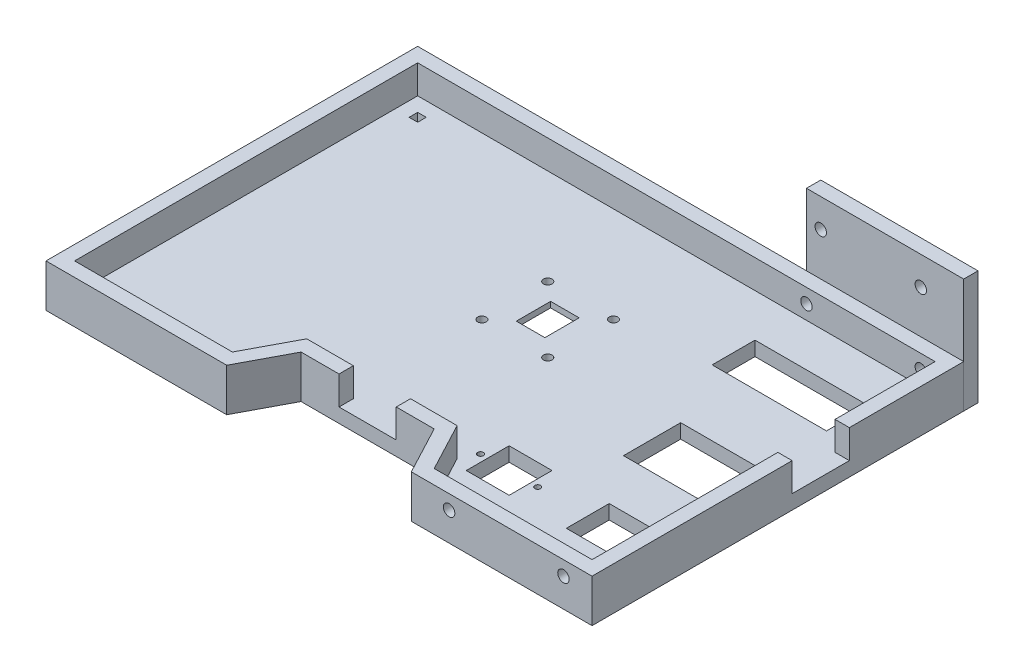
SolidWorks part; units mm, degrees
ref_plane "Front Plane" through (0, 0, 0) normal (0, 0, 1) x (1, 0, 0)
ref_plane "Top Plane" through (0, 0, 0) normal (0, 1, 0) x (1, 0, 0)
ref_plane "Right Plane" through (0, 0, 0) normal (1, 0, 0) x (0, 0, -1)
sketch "Sketch1" plane through (0, 0, 0) normal (0, 1, 0) x (1, 0, 0)
  line L0 (-36.5, -58) -> (-27.5, -41)
  line L1 (-88.5, 58) -> (88.5, 58)
  line L2 (-88.5, 58) -> (-88.5, -58)
  line L3 (-88.5, -58) -> (88.5, -58)
  line L4 (88.5, 58) -> (88.5, -58)
  line L5 (-27.5, -41) -> (27.5, -41)
  line L6 (27.5, -41) -> (36.5, -58)
  line L8 (-36.5, -58) -> (36.5, -58)
  line L9 (0, -63.8) -> (0, 63.8) construction
  line L10 (-97.35, 0) -> (97.35, 0) construction
  circle A0 centre (-84, 53.5) radius 1.5
  circle A1 centre (84, 53.5) radius 1.5
  circle A2 centre (-84, -53.5) radius 1.5
  circle A3 centre (84, -53.5) radius 1.5
  point P4 (0, 58)
  point P6 (88.5, 0)
  point P12 (0, -41)
  point P13 (0, -58)
  dimension "D7" = 3
  dimension "D1" = 116
  dimension "D2" = 177
  dimension "D3" = 73
  dimension "D4" = 55
  dimension "D5" = 17
  dimension "D8" = 4.5
  dimension "D9" = 4.5
sketch "Sketch3" plane through (0, 0, 0) normal (0, 1, 0) x (1, 0, 0)
  line L8 (95.5, 65) -> (-95.5, 65)
  line L9 (95.5, -65) -> (95.5, 65)
  line L10 (-95.5, -65) -> (95.5, -65)
  line L11 (-95.5, 65) -> (-95.5, -65)
  line L12 (95.5, 65) -> (-95.5, 65)
  line L13 (95.5, -65) -> (95.5, 65)
  line L14 (-95.5, -65) -> (-32.2854, -65)
  line L15 (-95.5, 65) -> (-95.5, -65)
  line L17 (32.2854, -65) -> (95.5, -65)
  line L20 (-30.3135, -61.2752) -> (-23.2854, -48)
  line L21 (23.2854, -48) -> (30.3135, -61.2752)
  line L22 (-23.2854, -48) -> (23.2854, -48)
  line L23 (-32.2854, -65) -> (-23.2854, -48)
  line L24 (23.2854, -48) -> (32.2854, -65)
  line L25 (-23.2854, -48) -> (23.2854, -48)
  dimension "D1" = 7
  dimension "D2" = 7
extrude "Boss-Extrude2" add sketch "Sketch3" along normal blind 15
shell "Shell1" thickness 5 removed face at (0, 15, 28.25)
sketch "Sketch4" plane through (0, 0, 0) normal (0, 1, 0) x (1, 0, 0)
  line L0 (-88.5, -58) -> (88.5, -58) construction
  line L1 (-5, 21) -> (5, 21)
  line L2 (-5, 21) -> (-5, 9)
  line L3 (-5, 9) -> (5, 9)
  line L4 (5, 21) -> (5, 9)
  line L5 (90.5, -60) -> (90.5, 60) construction
  line L6 (54.5, 7) -> (81.5, 7)
  line L7 (54.5, 7) -> (54.5, -13)
  line L8 (54.5, -13) -> (81.5, -13)
  line L9 (81.5, 7) -> (81.5, -13)
  line L10 (90.5, -60) -> (90.5, 60) construction
  line L11 (66.5, -30) -> (81.5, -30)
  line L12 (66.5, -30) -> (66.5, -45)
  line L13 (66.5, -45) -> (81.5, -45)
  line L14 (81.5, -30) -> (81.5, -45)
  line L16 (46.5, -30) -> (46.5, -45)
  line L17 (46.5, -45) -> (31.5, -45)
  line L18 (31.5, -30) -> (31.5, -45)
  line L19 (46.5, -30) -> (31.5, -30)
  line L20 (29, -37.5) -> (49, -37.5) construction
  line L21 (90.5, 60) -> (-90.5, 60) construction
  line L22 (42.5, 45) -> (82.5, 45)
  line L23 (42.5, 45) -> (42.5, 30)
  line L24 (42.5, 30) -> (82.5, 30)
  line L25 (82.5, 45) -> (82.5, 30)
  circle A0 centre (29, -37.5) radius 1
  circle A1 centre (49, -37.5) radius 1
  point P6 (0, 9)
  point P28 (39, -37.5)
  point P29 (31.5, -37.5)
  point P30 (39, -30)
  dimension "D10" = 2
  dimension "D1" = 67
  dimension "D2" = 12
  dimension "D3" = 10
  dimension "D4" = 65
  dimension "D5" = 20
  dimension "D6" = 9
  dimension "D7" = 27
  dimension "D8" = 13
  dimension "D9" = 15
  dimension "D11" = 20
  dimension "D12" = 15
  dimension "D13" = 40
  dimension "D14" = 8
  dimension "D15" = 15
  dimension "D16" = 15
  dimension "D17" = 15
  dimension "D18" = 20
extrude "Cut-Extrude2" cut sketch "Sketch4" against normal through all and the other way through all
sketch "Sketch5" plane through (0, 0, 0) normal (0, 1, 0) x (1, 0, 0)
  line L0 (0, -8.25) -> (0, 8.25) construction
  line L1 (-85.5, 55) -> (-82.5, 55)
  line L2 (-85.5, 55) -> (-85.5, 52)
  line L3 (-85.5, 52) -> (-82.5, 52)
  line L4 (-82.5, 55) -> (-82.5, 52)
  line L5 (82.5, 55) -> (82.5, 52)
  line L6 (85.5, 52) -> (82.5, 52)
  line L7 (85.5, 55) -> (85.5, 52)
  line L8 (85.5, 55) -> (82.5, 55)
  line L9 (-8.25, 0) -> (8.25, 0) construction
  line L10 (85.5, -55) -> (82.5, -55)
  line L11 (85.5, -55) -> (85.5, -52)
  line L12 (85.5, -52) -> (82.5, -52)
  line L13 (82.5, -55) -> (82.5, -52)
  line L14 (-82.5, -55) -> (-82.5, -52)
  line L15 (-85.5, -52) -> (-82.5, -52)
  line L16 (-85.5, -55) -> (-85.5, -52)
  line L17 (-85.5, -55) -> (-82.5, -55)
  circle A0 centre (-84, 53.5) radius 1.5 construction
extrude "Cut-Extrude4" cut sketch "Sketch5" along normal through all
sketch "Sketch6" plane through (0, 0, -65) normal (0, 0, -1) x (-1, 0, 0)
  line L2 (-95.5, 40) -> (-95.5, 0)
  line L3 (-95.5, 0) -> (-40.5, 0)
  line L5 (-95.5, 15) -> (-95.5, 0) construction
  line L13 (-40.5, 40) -> (-40.5, 0)
  line L14 (-40.5, 40) -> (-95.5, 40)
  circle A1 centre (-80.5, 30) radius 2
  circle A2 centre (-45.5, 30) radius 2
  point P14 (-95.5, 65)
  point P18 (95.5, 65)
  dimension "D1" = 35
  dimension "D2" = 4
  dimension "D3" = 30
  dimension "D4" = 15
  dimension "D5" = 55
  dimension "D6" = 40
extrude "Boss-Extrude3" add sketch "Sketch6" along normal blind 5 separate body
sketch "Sketch7" plane through (0, 0, -70) normal (0, 0, -1) x (-1, 0, 0)
  line L0 (-95.5, 0) -> (-40.5, 0) construction
  circle A0 centre (-85.5, 10) radius 2
  circle A2 centre (-45.5, 10) radius 2
  point P2 (0, 0)
  dimension "D1" = 4
  dimension "D4" = 40
  dimension "D2" = 10
  dimension "D3" = 10
extrude "Cut-Extrude5" cut sketch "Sketch7" against normal through all and the other way through all
sketch "Sketch8" plane through (0, 0, -65) normal (0, 0, 1) x (1, 0, 0)
  line L71 (45.5, 65) -> (20.5, 40) construction
  line L72 (80.5, 65) -> (45.5, 65) construction
  line L73 (95.5, 40) -> (80.5, 65) construction
  line L74 (95.5, 40) -> (95.5, 0) construction
  line L75 (45.5, 65) -> (20.5, 40)
  line L76 (80.5, 65) -> (45.5, 65)
  line L77 (95.5, 40) -> (80.5, 65)
  line L78 (95.5, 40) -> (95.5, 15)
  line L79 (90.5, 15) -> (95.5, 15)
  line L88 (90.5, 40) -> (90.5, 0)
  line L97 (90.5, 40) -> (90.5, 15)
  line L98 (32.2854, 15) -> (95.5, 15) construction
  line L99 (-95.5, 15) -> (-90.5, 15)
  line L100 (-95.5, 50) -> (-95.5, 0) construction
  line L101 (-80.5, 65) -> (-95.5, 50) construction
  line L102 (-45.5, 65) -> (-80.5, 65) construction
  line L103 (-20.5, 40) -> (-45.5, 65) construction
  line L104 (20.5, 40) -> (-20.5, 40) construction
  line L105 (-95.5, 50) -> (-95.5, 15)
  line L106 (-80.5, 65) -> (-95.5, 50)
  line L107 (-45.5, 65) -> (-80.5, 65)
  line L108 (-20.5, 40) -> (-45.5, 65)
  line L109 (20.5, 40) -> (-20.5, 40)
  dimension "D1" = 5
extrude "Boss-Extrude4" [suppressed] add sketch "Sketch8" along normal up to surface (130 mm away)
sketch "Sketch9" plane through (0, 0, -65) normal (0, 0, 1) x (1, 0, 0)
  line L0 (80.5, 30) -> (45.5, 30) construction
  circle A0 centre (63, 38) radius 10
  circle A1 centre (63, 38) radius 2.5
  point P2 (63, 30)
  dimension "D2" = 20
  dimension "D3" = 5
  dimension "D1" = 8
extrude "Boss-Extrude5" [suppressed] add sketch "Sketch9" along normal blind 20 from offset 38 separate body
chamfer "Chamfer2" distance 3 angle 45 4 edges at (0, 0, -21) (5, 0, -15) (0, 0, -9) (-5, 0, -15)
sketch "Sketch10" plane through (0, 0, 0) normal (0, -1, 0) x (1, 0, 0)
  line L0 (11.5, -3.5) -> (11.5, -26.5) construction
  line L1 (5, -21) -> (5, -9) construction
  line L2 (0, -8.25) -> (0, 8.25) construction
  line L4 (-15, 0) -> (15, 0) construction
  line L5 (-15, 0) -> (-15, -30) construction
  line L6 (-15, -30) -> (15, -30) construction
  line L7 (15, 0) -> (15, -30) construction
  circle A0 centre (11.5, -3.5) radius 1.5
  circle A1 centre (11.5, -26.5) radius 1.5
  circle A2 centre (-11.5, -26.5) radius 1.5
  circle A3 centre (-11.5, -3.5) radius 1.5
  point P7 (5, -15)
  point P8 (11.5, -15)
  point P10 (0, 0)
  dimension "D1" = 3
  dimension "D2" = 3.5
  dimension "D4" = 30
  dimension "D5" = 30
  dimension "D6" = 3.5
  dimension "D7" = 3.5
extrude "Cut-Extrude6" cut sketch "Sketch10" against normal blind 5
sketch "Sketch11" plane through (0, 0, 48) normal (0, 0, 1) x (1, 0, 0)
  line L0 (-23.2854, 15) -> (23.2854, 15) construction
  line L1 (-10, 15) -> (10, 15)
  line L2 (-10, 15) -> (-10, 5)
  line L3 (-10, 5) -> (10, 5)
  line L4 (10, 15) -> (10, 5)
  point P6 (0, 15)
  dimension "D1" = 10
  dimension "D2" = 20
extrude "Cut-Extrude7" cut sketch "Sketch11" against normal blind 5 contours L2 L3 L4 L1
sketch "Sketch12" plane through (95.5, 0, 0) normal (1, 0, 0) x (0, 0, -1)
  line L1 (5, 20) -> (25, 20)
  line L2 (5, 20) -> (5, 5)
  line L3 (5, 5) -> (25, 5)
  line L4 (25, 20) -> (25, 5)
  line L5 (21, 0) -> (9, 0) construction
  line L6 (21, 0) -> (9, 0) construction
  point P4 (15, 0)
  point P5 (15, 5)
  dimension "D1" = 20
  dimension "D2" = 15
  dimension "D3" = 5
extrude "Cut-Extrude8" cut sketch "Sketch12" against normal blind 6
fillet "Fillet1" [suppressed] radius 3
